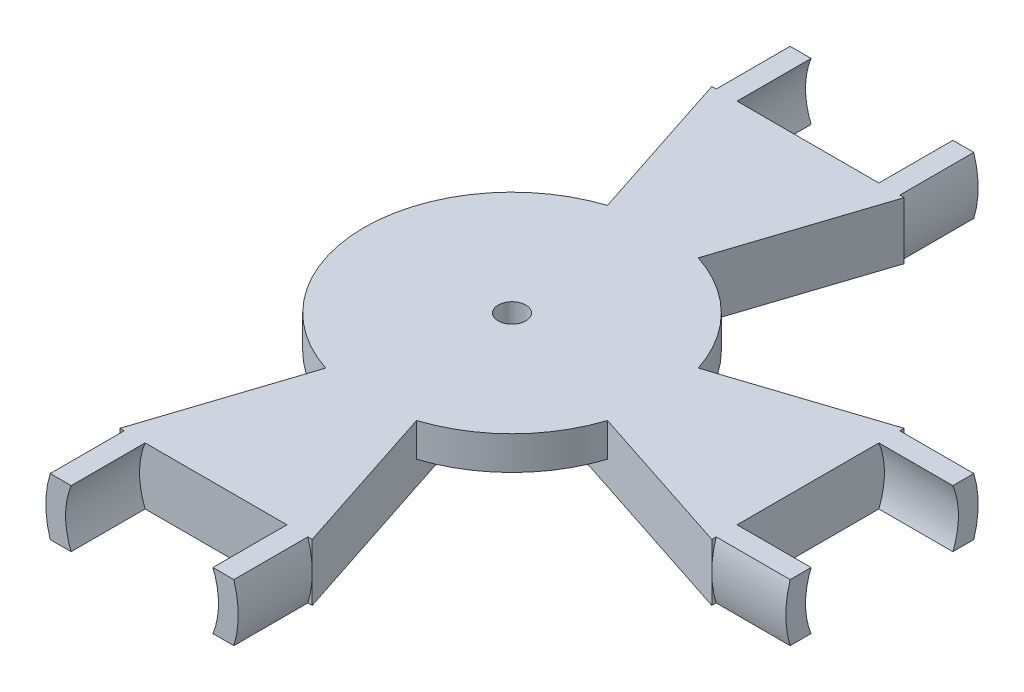
SolidWorks part; units mm, degrees
material "Polyethylene Cross-Linked"
ref_plane "Front Plane" through (0, 0, 0) normal (0, 0, 1) x (1, 0, 0)
ref_plane "Top Plane" through (0, 0, 0) normal (0, 1, 0) x (1, 0, 0)
ref_plane "Right Plane" through (0, 0, 0) normal (1, 0, 0) x (0, 0, -1)
sketch "Sketch1" plane through (0, 0, 0) normal (0, 1, 0) x (1, 0, 0)
  circle A0 centre (0, 0) radius 6.35
  dimension "D1" = 12.7
extrude "Boss-Extrude1" add sketch "Sketch1" along normal blind 5.4
sketch "Sketch2" plane through (0, 5.4, 0) normal (0, 1, 0) x (1, 0, 0)
  line L0 (0, 0) -> (0, 16.53) construction
  line L1 (-2.6097, 16.9902) -> (-4.8916, 4.049)
  line L2 (0, 19.18) -> (0, 16.53) construction
  line L3 (2.6097, 16.9902) -> (4.8916, 4.049)
  arc A0 (2.6097, 16.9902) -> (-2.6097, 16.9902) centre (0, 16.53) ccw
  arc A4 (4.8916, 4.049) -> (-4.8916, 4.049) centre (0, 0) ccw
  circle A5 centre (0, 0) radius 6.35 construction
  dimension "D1" = 5.3
  dimension "D2" = 19.18
  dimension "D3" = 10
  dimension "D4" = 9.7832
extrude "horn" add sketch "Sketch2" against normal blind 2.5
sketch "Sketch4" plane through (0, 5.4, 0) normal (0, -1, 0) x (-1, 0, 0)
  circle A0 centre (0, 0) radius 1.4
  dimension "D1" = 2.8
extrude "Cut-Extrude1" cut sketch "Sketch4" along normal through all
sketch "Sketch5" plane through (0, 0, 0) normal (0, -1, 0) x (-1, 0, 0)
  circle A0 centre (0, 16.53) radius 0.5
  dimension "D1" = 1
extrude "Cut-Extrude2" cut sketch "Sketch5" against normal through all
sketch "Sketch6" plane through (0, 0, 0) normal (0, 1, 0) x (1, 0, 0)
  line L0 (0, 0) -> (0, 16.53) construction
pattern_linear "LPattern1" count 4 spacing 3 along (0, 0, 1) of "Cut-Extrude2"
mirror "Mirror1" about plane through (0, 0, 0) normal (0, 0, 1) of "horn", "LPattern1", "Cut-Extrude2"
sketch "Sketch8" plane through (0, 0, 0) normal (0, -1, 0) x (-1, 0, 0)
  line L0 (0, -2.9) -> (0.2629, -2.5867)
  line L1 (0, -2.9) -> (-0.2629, -2.5867)
  line L2 (0, -2.6) -> (0, -2.9) construction
  line L3 (0, 0) -> (0, -2.6) construction
  arc A1 (-0.2629, -2.5867) -> (0.2629, -2.5867) centre (0, 0) ccw
  dimension "D1" = 0.3
  dimension "D2" = 5.2
  dimension "D3" = 80
extrude "Cut-Extrude4" cut sketch "Sketch8" against normal blind 3
pattern_circular "CirPattern2" count 26 over 360 about axis through (0, 0, 0) along (0, 1, 0) of "Cut-Extrude4"
sketch "Sketch9" plane through (0, 0, 0) normal (0, -1, 0) x (-1, 0, 0)
  circle A0 centre (0, 0) radius 2.6
  arc A1 (-0.2629, -2.5867) -> (0.2629, -2.5867) centre (0, 0) ccw construction
extrude "Cut-Extrude5" cut sketch "Sketch9" against normal blind 3
sketch "Sketch10" plane through (0, 0, 0) normal (0, -1, 0) x (-1, 0, 0)
  circle A0 centre (0, 0) radius 6.35
  circle A1 centre (0, 0) radius 4.25
  circle A2 centre (0, 0) radius 6.35 construction
  dimension "D1" = 8.5
extrude "Cut-Extrude6" cut sketch "Sketch10" against normal up to surface (2.9 mm away) up to face at (0, 2.9, 11.03)
sketch "Sketch11" plane through (0, 0, 0) normal (0, 0, 1) x (1, 0, 0)
  line L2 (4.21, 0.99) -> (5.8127, 2.9)
  line L3 (4.8916, 2.9) -> (6.35, 2.9) construction
  line L4 (5.8127, 2.9) -> (4.21, 2.9)
  line L7 (4.21, 0.99) -> (4.16, 0.99)
  line L8 (4.16, 0.99) -> (4.16, 2.9)
  line L10 (4.21, 0.99) -> (4.21, 2.9) construction
  line L12 (4.16, 2.9) -> (4.21, 2.9)
  line L13 (0, 2.9) -> (4.16, 2.9) construction
  line L14 (-4.25, 2.9) -> (4.25, 2.9) construction
  dimension "D1" = 1.91
  dimension "D2" = 0.05
  dimension "D3" = 40
  dimension "D4" = 4.16
extrude "Boss-Extrude5" add sketch "Sketch11" along normal mid plane 1
pattern_circular "CirPattern3" count 4 over 360 about axis through (0, 5.4, 0) along (0, -1, 0) of "Boss-Extrude5"
sketch "Sketch12" plane through (0, 5.4, 0) normal (0, 1, 0) x (1, 0, 0)
  circle A0 centre (0, 0) radius 4.375
  dimension "D1" = 8.75
extrude "Cut-Extrude7" cut sketch "Sketch12" against normal blind 1
sketch "Sketch13" plane through (0, 4.4, 0) normal (0, 1, 0) x (1, 0, 0)
  circle A0 centre (0, 0) radius 2.875
  circle A1 centre (0, 0) radius 3.375
  dimension "D1" = 0.5
  dimension "D2" = 6.75
extrude "Boss-Extrude6" add sketch "Sketch13" along normal up to surface (1 mm away) up to face at (0, 5.4, 4.375)
sketch "Sketch14" plane through (0, 5.4, 0) normal (0, 1, 0) x (1, 0, 0)
  circle A0 centre (0, 0) radius 2.875
  circle A1 centre (0, 0) radius 2.875 construction
  circle A2 centre (0, 0) radius 3.375
  circle A3 centre (0, 0) radius 3.375 construction
extrude "Boss-Extrude7" add sketch "Sketch14" along normal blind 0.35
ref_plane "Plane1" through (0, 0, 30) normal (0, 0, 1) x (1, 0, 0)
sketch "Sketch16" plane through (0, 0, 30) normal (0, 0, 1) x (1, 0, 0)
  line L0 (-2.6097, 2.9) -> (2.6097, 2.9) construction
  line L1 (-7.187, 0) -> (-9.3087, 0)
  line L2 (7.187, 0) -> (9.3087, 0)
  line L3 (-9.3087, 5.8) -> (-7.187, 5.8)
  line L4 (7.187, 5.8) -> (9.3087, 5.8)
  circle A0 centre (0, 2.9) radius 7.75 construction
  circle A1 centre (0, 2.9) radius 9.75 construction
  arc A2 (-9.3087, 0) -> (-9.3087, 5.8) centre (0, 2.9) cw
  arc A3 (-7.187, 5.8) -> (-7.187, 0) centre (0, 2.9) ccw
  arc A4 (7.187, 5.8) -> (7.187, 0) centre (0, 2.9) cw
  arc A5 (9.3087, 5.8) -> (9.3087, 0) centre (0, 2.9) cw
  dimension "D1" = 15.5
  dimension "D2" = 2
extrude "Boss-Extrude8" add sketch "Sketch16" along normal blind 7.5 separate body
sketch "Sketch18" plane through (0, 2.9, 0) normal (0, -1, 0) x (1, 0, 0)
  line L0 (0, 0) -> (-9.3087, 30) construction
  line L1 (-9.3087, 30) -> (9.3087, 30) construction
  line L2 (9.3087, 30) -> (0, 0) construction
  line L3 (-1.2595, 4.0591) -> (-9.75, 30)
  line L4 (-9.75, 30) -> (9.75, 30)
  line L5 (9.75, 30) -> (1.2595, 4.0591)
  line L6 (4.0591, 1.2595) -> (30, 9.75)
  line L7 (30, 9.75) -> (30, -9.75)
  line L8 (30, -9.75) -> (4.0591, -1.2595)
  line L9 (30, 9.3087) -> (30, -9.3087) construction
  line L10 (1.2595, -4.0591) -> (9.75, -30)
  line L11 (9.75, -30) -> (-9.75, -30)
  line L12 (-9.75, -30) -> (-1.2595, -4.0591)
  line L13 (9.3087, -30) -> (-9.3087, -30) construction
  line L14 (0, 0) -> (1.2595, 4.0591) construction
  line L15 (0, 0) -> (4.0591, -1.2595) construction
  arc A0 (-1.2595, 4.0591) -> (1.2595, 4.0591) centre (0, 0) cw
  circle A1 centre (0, 0) radius 4.25 construction
  arc A2 (4.0591, 1.2595) -> (4.0591, -1.2595) centre (0, 0) cw
  arc A3 (1.2595, -4.0591) -> (-1.2595, -4.0591) centre (0, 0) cw
  dimension "D2" = 90
  dimension "D1" = 3
extrude "Boss-Extrude9" add sketch "Sketch18" along normal up to vertex (2.9 mm away) and the other way up to vertex (2.9 mm away) up to point (9.3087, 0, 30) other way up to point (9.3087, 5.8, 30)
ref_axis "Axis1" through (0, -0.2901, 0) along (0, 1, 0)
sketch "Sketch19" plane through (0, 0, -30) normal (0, 0, -1) x (-1, 0, 0)
  line L0 (0, 3) -> (0, 0) construction
  line L1 (-9.3087, 5.8) -> (-7.187, 5.8)
  line L2 (-9.3087, 0) -> (-7.187, 0)
  line L3 (7.187, 5.8) -> (9.3087, 5.8)
  line L4 (7.187, 0) -> (9.3087, 0)
  arc A0 (7.187, 5.8) -> (7.187, 0) centre (0, 2.9) cw
  arc A1 (9.3087, 5.8) -> (9.3087, 0) centre (0, 2.9) cw
  arc A2 (7.187, 0) -> (7.187, 5.8) centre (0, 2.9) ccw construction
  arc A3 (9.75, 2.9) -> (9.3087, 5.8) centre (0, 2.9) ccw construction
  arc A4 (-9.3087, 5.8) -> (-9.3087, 0) centre (0, 2.9) ccw
  arc A5 (-7.187, 5.8) -> (-7.187, 0) centre (0, 2.9) ccw
extrude "Boss-Extrude10" add sketch "Sketch19" along normal blind 7.5
sketch "Sketch21" plane through (30, 0, 0) normal (1, 0, 0) x (0, 0, -1)
  line L0 (-9.75, 5.8) -> (9.75, 0) construction
  line L1 (30, 0) -> (4.0591, 0) construction
  line L2 (9.75, 0) -> (9.75, 5.8) construction
  line L3 (-9.75, 0) -> (9.75, 5.8) construction
  line L4 (9.75, 5.8) -> (-9.75, 5.8) construction
  line L5 (9.75, 0) -> (-9.75, 0) construction
  line L6 (7.187, 5.8) -> (9.3087, 5.8)
  line L7 (9.3087, 0) -> (7.187, 0)
  line L8 (0, 2.9) -> (0, 5.8) construction
  line L9 (-7.187, 5.8) -> (-9.3087, 5.8)
  line L10 (-9.3087, 0) -> (-7.187, 0)
  arc A0 (7.187, 5.8) -> (7.187, 0) centre (0, 2.9) cw
  arc A1 (9.3087, 5.8) -> (9.3087, 0) centre (0, 2.9) cw
  arc A2 (-9.3087, 5.8) -> (-9.3087, 0) centre (0, 2.9) ccw
  arc A3 (-7.187, 5.8) -> (-7.187, 0) centre (0, 2.9) ccw
  point P14 (0, 2.9)
  dimension "D1" = 7.75
  dimension "D2" = 2
extrude "Boss-Extrude11" add sketch "Sketch21" along normal blind 7.5
sketch "Sketch22" plane through (0, 5.4, 0) normal (0, 1, 0) x (1, 0, 0)
  circle A0 centre (0, 0) radius 4.375
  circle A1 centre (0, 0) radius 15
  arc A2 (-1.2984, 4.1779) -> (-1.2984, -4.1779) centre (0, 0) ccw construction
  dimension "D1" = 30
extrude "Boss-Extrude12" add sketch "Sketch22" against normal blind 3 and the other way up to vertex (0.4 mm away) other way up to point (1.2595, 5.8, 4.0591)
sketch "Sketch23" plane through (0, 2.4, 0) normal (0, -1, 0) x (1, 0, 0)
  circle A0 centre (0, 0) radius 4.25
  circle A1 centre (0, 0) radius 5.25
  dimension "D1" = 1
extrude "Boss-Extrude13" add sketch "Sketch23" along normal up to vertex (2.4 mm away) up to point (-1.2595, 0, -4.0591)
sketch "Sketch24" plane through (0, 4.4, 0) normal (0, 1, 0) x (1, 0, 0)
  circle A0 centre (0, 0) radius 1.4
  circle A1 centre (0, 0) radius 7.1556
extrude "Boss-Extrude14" add sketch "Sketch24" along normal up to vertex (1.4 mm away) up to point (-1.2984, 5.8, 4.1779)
